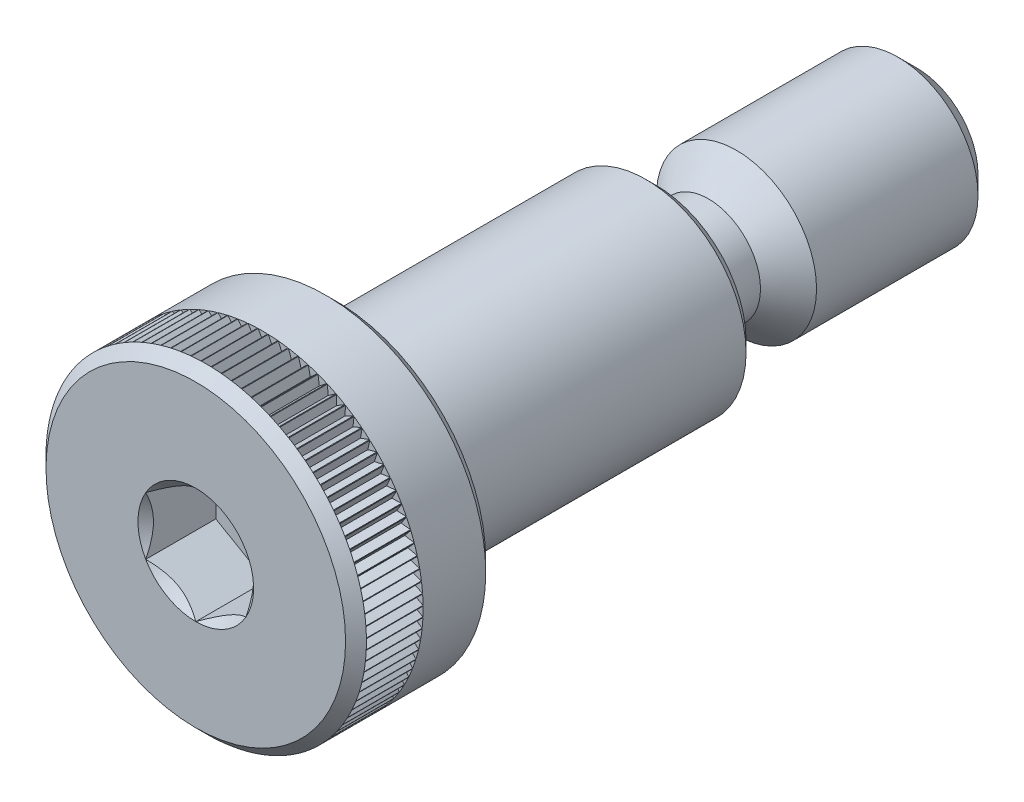
SolidWorks part; units mm, degrees
material "AISI 304"
ref_plane "Front Plane" through (0, 0, 0) normal (0, 0, 1) x (1, 0, 0)
ref_plane "Top Plane" through (0, 0, 0) normal (0, 1, 0) x (1, 0, 0)
ref_plane "Right Plane" through (0, 0, 0) normal (1, 0, 0) x (0, 0, -1)
sketch "Sketch1" plane through (0, 0, 0) normal (1, 0, 0) x (0, 0, -1)
  line L0 (-18, 0) -> (18, 0) construction
  line L1 (-18, -8) -> (-18, 8) construction
  line L2 (-18, 8) -> (-11, 8) construction
  line L3 (-11, 8) -> (-11, 4.797) construction
  line L4 (-11, 4.797) -> (-10.492, 4.797) construction
  line L5 (-10.492, 4.797) -> (-10.289, 5) construction
  line L6 (-10.289, 5) -> (5, 5) construction
  line L7 (17.9219, 4.1353) -> (18.5469, 3.0528) construction
  line L8 (18.5469, 3.0528) -> (19.1719, 4.1353) construction
  line L9 (18, -4) -> (18, 4) construction
  line L10 (5, 5) -> (18, 5) construction
  line L11 (19.1719, 4.1353) -> (17.9219, 4.1353) construction
  line L12 (18.5469, 4.1353) -> (18.5469, 4) construction
  line L13 (18.5469, 3.0528) -> (18.5469, 3.1881) construction
  line L14 (18.625, 3.1881) -> (18.4688, 3.1881) construction
  line L15 (19.0937, 4) -> (18, 4) construction
  line L16 (18.5469, 4.0677) -> (19.1328, 4.0677) construction
  line L17 (18.5469, 4.0677) -> (17.9609, 4.0677) construction
  line L18 (-18, 7.48) -> (-17.48, 8) construction
  line L19 (-11.52, 8) -> (-11, 7.48) construction
  line L20 (18, 4) -> (5, 4) construction
  line L21 (17.0625, 4) -> (18, 3.0625) construction
  line L22 (9, 4) -> (7.6, 2.6) construction
  line L23 (7.6, 2.6) -> (5.7, 2.6) construction
  line L24 (5, 4) -> (5, 3.3) construction
  line L25 (-14.5, 2.5) -> (-14.5, -2.5) construction
  line L26 (-14.5, -2.5) -> (-18, -2.5) construction
  line L27 (-14.5, 2.5) -> (-18, 2.5) construction
  line L28 (-17.48, 0) -> (-14.649, 0) construction
  arc A0 (5, 3.3) -> (5.7, 2.6) centre (5.7, 3.3) ccw construction
  point P4 (0, 0)
  point P7 (-18, 0)
  point P18 (18, 0)
  point P25 (13.625, -4)
  point P38 (-14.5, 8)
  point P45 (-14.5, 0)
  point P46 (8.3, 3.3)
  point P48 (-10.492, 0)
  point P51 (-14.5, 0)
  point P52 (5, 0)
  dimension "Head Diameter" = 16
  dimension "Head Height" = 7
  dimension "Thread Diameter" = 8
  dimension "Shoulder Diameter" = 10
  dimension "Thread Length" = 13
  dimension "D1" = 0.508
  dimension "D2" = 135
  dimension "D3" = 0.203
  dimension "Shoulder Length" = 16
  dimension "Thread Pitch" = 1.25
  dimension "D4" = 0.1562
  dimension "D5" = 4.375
  dimension "D6" = 0.52
  dimension "D7" = 0.9375
  dimension "D8" = 5.2
  dimension "D9" = 2.6
  dimension "Drive Size" = 5
  dimension "Knurling Length" = 2.831
sketch "Sketch3" plane through (0, 0, 0) normal (1, 0, 0) x (0, 0, -1)
  line L0 (-18, 0) -> (-18, 7.48)
  line L1 (-18, -8) -> (-18, 8) construction
  line L2 (-18, 7.48) -> (-17.48, 8)
  line L3 (-17.48, 8) -> (-11.52, 8)
  line L4 (-11.52, 8) -> (-11, 7.48)
  line L5 (-11, 7.48) -> (-11, 4.797)
  line L6 (-11, 4.797) -> (-10.492, 4.797)
  line L7 (-10.492, 4.797) -> (-10.289, 5)
  line L8 (-10.289, 5) -> (5, 5)
  line L9 (5, 5) -> (5, 3.3)
  line L10 (5.7, 2.6) -> (7.6, 2.6)
  line L11 (7.6, 2.6) -> (9, 4)
  line L12 (9, 4) -> (17.0625, 4)
  line L13 (17.0625, 4) -> (18, 3.0625)
  line L14 (18, 3.0625) -> (18, 0)
  line L15 (18, 0) -> (-18, 0)
  arc A0 (5, 3.3) -> (5.7, 2.6) centre (5.7, 3.3) ccw construction
  arc A1 (5, 3.3) -> (5.7, 2.6) centre (5.7, 3.3) ccw
revolve "Revolve1" add sketch "Sketch3" angle 360 about L0
sketch "Sketch4" plane through (0, 0, 0) normal (0, 0, 1) x (1, 0, 0)
  line L0 (0, -8) -> (0, 8) construction
  line L1 (0, 2.8868) -> (-2.5, 1.4434)
  line L2 (-2.5, 1.4434) -> (-2.5, -1.4434)
  line L3 (-2.5, -1.4434) -> (0, -2.8868)
  line L4 (0, -2.8868) -> (2.5, -1.4434)
  line L5 (2.5, -1.4434) -> (2.5, 1.4434)
  line L6 (2.5, 1.4434) -> (0, 2.8868)
  circle A0 centre (0, 0) radius 2.5 construction
extrude "Cut-Extrude1" cut sketch "Sketch4" against normal up to vertex (-14.5 mm away) from vertex up to point (0, 0, 14.5) starting at point (0, 0, 18)
sketch "Sketch5" plane through (0, 0, 0) normal (0, 0, 1) x (1, 0, 0)
  line L0 (0, -8) -> (0, 8) construction
  circle A0 centre (0, 0) radius 2.8868
extrude "Cut-Extrude2" cut sketch "Sketch5" against normal up to vertex (-14.5 mm away) draft 45 from vertex up to point (0, 0, 14.5) starting at point (0, 0, 18)
chamfer "Chamfer1" distance 0.52 angle 45 1 edges at (5, 0, -5)
sketch "Sketch6" plane through (0, 0, -18) normal (0, 0, -1) x (-1, 0, 0)
  circle A0 centre (0, 0) radius 4
curve "Helix/Spiral1" pitch 1.25 height 12.35 turns 9.88
sketch "Sketch7" plane through (0, 0, 0) normal (1, 0, 0) x (0, 0, -1)
  line L0 (17.9609, 4.0677) -> (18.4688, 3.1881)
  line L1 (18.4688, 3.1881) -> (18.625, 3.1881)
  line L2 (18.625, 3.1881) -> (19.1328, 4.0677)
  line L3 (19.1328, 4.0677) -> (17.9609, 4.0677)
sweep "Cut-Sweep1" [suppressed] cut profiles "Sketch7" path "Helix/Spiral1"
sketch "Sketch8" plane through (0, 0, 0) normal (0, 0, 1) x (1, 0, 0)
  line L0 (0, 8) -> (0, 0) construction
  line L1 (-0.2402, 8) -> (0.2402, 8)
  line L2 (0.2402, 8) -> (0, 7.584)
  line L3 (0, 7.584) -> (-0.2402, 8)
  line L4 (-0.2402, 8) -> (0, 0) construction
  line L5 (0, 0) -> (0.2402, 8) construction
  circle A0 centre (0, 0) radius 7.584 construction
  point P8 (0, 8)
  dimension "D1" = 0.416
  dimension "D2" = 3.439
extrude "Cut-Extrude3" cut sketch "Sketch8" against normal up to vertex (-14.649 mm away) from vertex up to point (0, 0, 14.649) starting at point (0, 0, 17.48)
pattern_circular "CirPattern1" count 99 over 360 about axis through (0, 0, 18) along (0, 0, -1) of "Cut-Extrude3"
equation "\"D4@Sketch1\"=\"Thread Pitch@Sketch1\"/8"
equation "\"D5@Sketch1\"=\"Thread Pitch@Sketch1\"*3.5"
equation "\"D6@Sketch1\"=\"Head Diameter@Sketch1\"*.0325"
equation "\"D7@Sketch1\"=\"Thread Pitch@Sketch1\"*.75"
equation "\"D8@Sketch1\"=\"Thread Diameter@Sketch1\"*.65"
equation "\"D9@Sketch1\"=\"Thread Length@Sketch1\"*.2"
equation "\"D1@Chamfer1\"=\"D6@Sketch1\""
equation "\"D4@Helix/Spiral1\"=\"Thread Pitch@Sketch1\""
equation "\"D3@Helix/Spiral1\"=\"Thread Length@Sketch1\"*.95"
equation "\"D1@Sketch8\"=\"D6@Sketch1\"*.8"
equation "\"D1@CirPattern1\"=(360/\"D2@Sketch8\")-6"
equation "\"D1@Cut-Extrude3\"=\"D11@Sketch1\""
